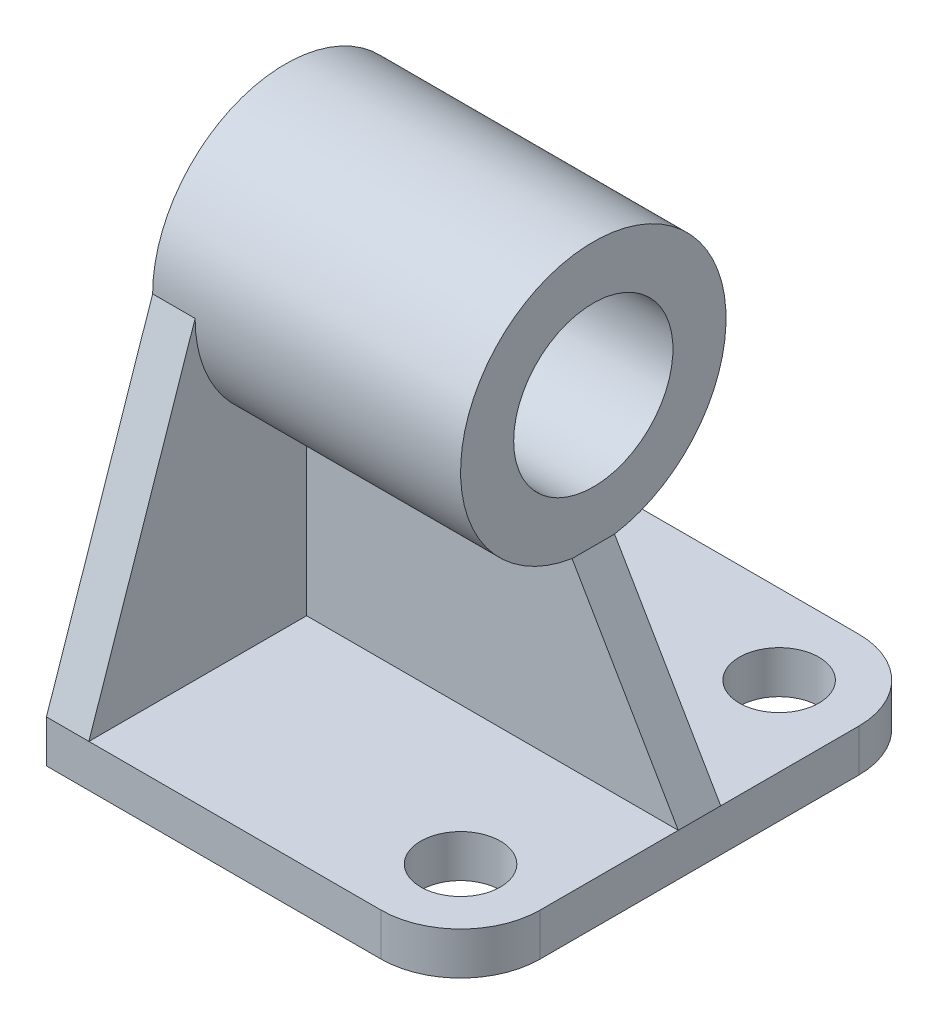
SolidWorks part; units mm, degrees
ref_plane "Front Plane" through (0, 0, 0) normal (0, 0, 1) x (1, 0, 0)
ref_plane "Top Plane" through (0, 0, 0) normal (0, 1, 0) x (1, 0, 0)
ref_plane "Right Plane" through (0, 0, 0) normal (1, 0, 0) x (0, 0, -1)
sketch "Sketch2" plane through (0, 0, 0) normal (0, 1, 0) x (1, 0, 0)
  line L0 (-4.5451, -26.6223) -> (58.4549, -26.6223)
  line L1 (73.4549, -11.6223) -> (73.4549, 48.3777)
  line L2 (58.4549, 63.3777) -> (-4.5451, 63.3777)
  line L3 (-4.5451, 63.3777) -> (-4.5451, -26.6223)
  arc A0 (58.4549, -26.6223) -> (73.4549, -11.6223) centre (58.4549, -11.6223) ccw
  arc A1 (73.4549, 48.3777) -> (58.4549, 63.3777) centre (58.4549, 48.3777) ccw
  circle A2 centre (58.4549, -11.6223) radius 7.5
  circle A3 centre (58.4549, 48.3777) radius 7.5
  dimension "D1" = 15
  dimension "D2" = 15
  dimension "D3" = 15
  dimension "D4" = 60
  dimension "D5" = 63
extrude "Boss-Extrude1" add sketch "Sketch2" along normal blind 8
sketch "Sketch3" plane through (-4.5451, 0, 0) normal (-1, 0, 0) x (0, 0, 1)
  line L0 (-63.3777, 0) -> (26.6223, 0) construction
  line L1 (-18.3777, 8) -> (-18.3777, 67)
  line L2 (-63.3777, 8) -> (26.6223, 8) construction
  line L3 (-43.3777, 67) -> (-63.3777, 8)
  line L4 (-48.3777, 8) -> (-63.3777, 8) construction
  line L5 (-63.3777, 8) -> (26.6223, 8)
  line L6 (26.6223, 8) -> (6.6223, 67)
  circle A0 centre (-18.3777, 67) radius 15
  circle A1 centre (-18.3777, 67) radius 25
  line M8 (26.6223, 8) -> (-63.3777, 8)
  dimension "D2" = 30
  dimension "D3" = 50
  dimension "D1" = 59
extrude "Boss-Extrude3" add sketch "Sketch3" against normal blind 8 contours A1 L1 L6 M8 | A1 L3 L1 M8 region at (-4.5451, 27.9238, -38.6509) region at (-4.5451, 27.9238, 1.8954)
extrude "Boss-Extrude4" add sketch "Sketch3<4>" against normal blind 58 contours A1 A0 region at (-4.5451, 49.8223, -35.5554)
sketch "Sketch3<4>" plane through (-4.5451, 0, 0) normal (-1, 0, 0) x (0, 0, 1) same geometry as "Sketch3"
sketch "Sketch5" plane through (73.4549, 0, 0) normal (1, 0, 0) x (0, 0, -1)
  line L0 (-11.6223, 8) -> (48.3777, 8) construction
  line L1 (18.3777, 8) -> (18.3777, 67) construction
  point P2 (0, 0)
  point P6 (0, 0)
sketch "Sketch16" plane through (-4.5451, 0, 0) normal (-1, 0, 0) x (0, 0, 1)
sketch "Sketch17" plane through (-4.5451, 0, 0) normal (-1, 0, 0) x (0, 0, 1)
  line L0 (-18.3777, 8) -> (-18.3777, 67) construction
  line L2 (-22.3777, 47.5018) -> (-22.3777, 8)
  line L3 (-22.3777, 8) -> (-14.3777, 8)
  line L4 (-14.3777, 47.5018) -> (-14.3777, 8)
  line L5 (-19.7339, 47.5018) -> (-14.3777, 8) construction
  line L6 (-22.3777, 8) -> (-17.0216, 47.5018) construction
  line L7 (-22.3777, 47.5018) -> (-14.3777, 47.5018)
  point P0 (-18.3777, 37.5)
  dimension "D1" = 59
  dimension "D2" = 8
extrude "Boss-Extrude6" add sketch "Sketch17" against normal blind 78
sketch "Sketch18" plane through (0, 0, -22.3777) normal (0, 0, -1) x (-1, 0, 0)
  line L0 (-73.4549, 8) -> (-53.4549, 42.3221)
  line L1 (-53.4549, 42.3221) -> (-53.4549, 47.5018)
  line L2 (-53.4549, 47.5018) -> (-73.4549, 47.5018)
  line L3 (-73.4549, 47.5018) -> (-73.4549, 8)
extrude "Cut-Extrude1" cut sketch "Sketch18" against normal blind 78
